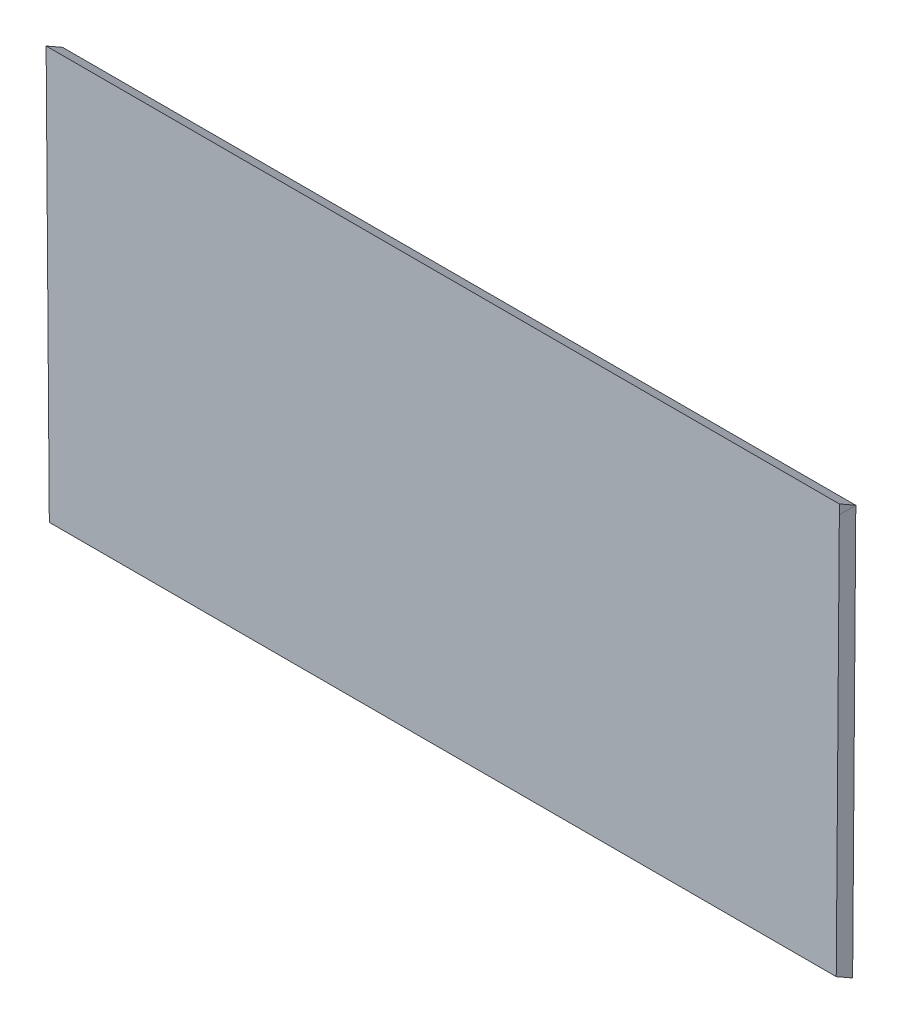
SolidWorks part; units mm, degrees
material "Verre"
ref_plane "Plan de face" through (0, 0, 0) normal (0, 0, 1) x (1, 0, 0)
ref_plane "Plan de dessus" through (0, 0, 0) normal (0, 1, 0) x (1, 0, 0)
ref_plane "Plan de droite" through (0, 0, 0) normal (1, 0, 0) x (0, 0, -1)
sketch "Esquisse1" plane through (0, 0, 0) normal (0, 0, 1) x (1, 0, 0)
  line L0 (-627.1025, 177.6284) -> (-621.2879, -571.009)
  line L1 (-621.2879, -571.009) -> (811.9021, -571.0092)
  line L2 (811.9021, -571.0092) -> (817.6975, 177.6284)
  line L3 (817.6975, 177.6284) -> (-627.1025, 177.6284)
  dimension "D1" = 748.66
  dimension "D2" = 1444.8
  dimension "D3" = 1433.19
extrude "Boss.-Extru.1" add sketch "Esquisse1" along normal blind 30
sketch "Esquisse2" plane through (0, 0, 0) normal (1, 0, 0) x (0, 0, -1)
  line L0 (0, 177.6284) -> (-30, 177.6284)
  line L1 (-30, 177.6284) -> (-30, 194.7679)
  line L2 (-30, 194.7679) -> (0, 177.6284)
  dimension "D1" = 29.74
extrude "Boss.-Extru.2" add sketch "Esquisse2" along normal blind 817.7 and the other way blind 627.1
sketch "Esquisse3" plane through (0, 0, 0) normal (1, 0, 0) x (0, 0, -1)
  line L0 (-30, -571.0092) -> (-30, -553.8697)
  line L1 (-30, -571.0092) -> (-30, 177.6284) construction
  line L2 (-30, -553.8697) -> (0, -571.0092)
  line L3 (0, -571.0092) -> (-30, -571.0092)
  dimension "D1" = 29.74
extrude "Enlèv. mat.-Extru.1" cut sketch "Esquisse3" against normal blind 817.7 and the other way blind 817.7
